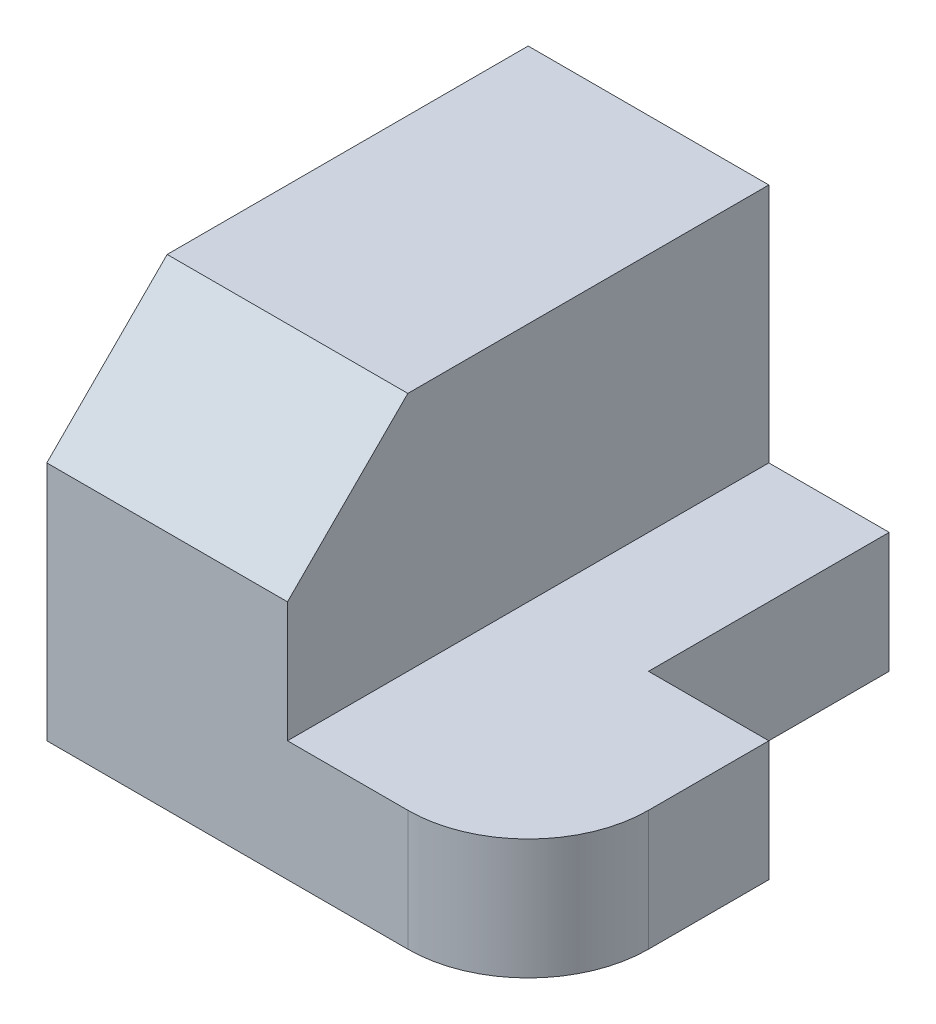
SolidWorks part; units mm, degrees
ref_plane "前基準面" through (0, 0, 0) normal (0, 0, 1) x (1, 0, 0)
ref_plane "上基準面" through (0, 0, 0) normal (0, 1, 0) x (1, 0, 0)
ref_plane "右基準面" through (0, 0, 0) normal (1, 0, 0) x (0, 0, -1)
sketch "草圖1" plane through (0, 0, 0) normal (0, 1, 0) x (1, 0, 0)
  line L0 (0, 0) -> (0, 40)
  line L1 (0, 40) -> (-20, 40)
  line L2 (-20, 40) -> (-20, 0)
  line L3 (-20, 0) -> (0, 0)
  line L4 (-20, 10) -> (0, 10)
  line L5 (0, 40) -> (10, 40)
  line L6 (10, 40) -> (10, 20)
  line L7 (10, 20) -> (20, 20)
  line L8 (20, 20) -> (20, 0)
  line L9 (0, 0) -> (20, 0)
  point P11 (0, 0)
  dimension "D1" = 10
  dimension "D2" = 20
  dimension "D3" = 20
  dimension "D4" = 20
  dimension "D5" = 10
  dimension "D6" = 20
extrude "填料-伸長1" add sketch "草圖1" along normal blind 20 contours L4 L2 L3 L0 region at (-10, 0, -5)
extrude "填料-伸長2" add sketch "草圖1<3>" along normal blind 10 contours L0 L9 L8 L7 L6 L5 region at (8.3333, 0, -16.6667)
sketch "草圖1<3>" plane through (0, 0, 0) normal (0, 1, 0) x (1, 0, 0) same geometry as "草圖1"
extrude "填料-伸長3" add sketch "草圖1<4>" along normal blind 30 contours L2 L4 L0 L1 region at (-10, 0, -25)
sketch "草圖1<4>" plane through (0, 0, 0) normal (0, 1, 0) x (1, 0, 0) same geometry as "草圖1"
sketch "草圖2" plane through (0, 0, 0) normal (1, 0, 0) x (0, 0, -1)
  line L0 (10, 30) -> (0, 20)
  line L1 (0, 20) -> (10, 20)
  line L2 (10, 20) -> (10, 30)
extrude "填料-伸長4" add sketch "草圖2" against normal blind 20
fillet "圓角1" radius 10 1 edges at (20, 5, 0)
